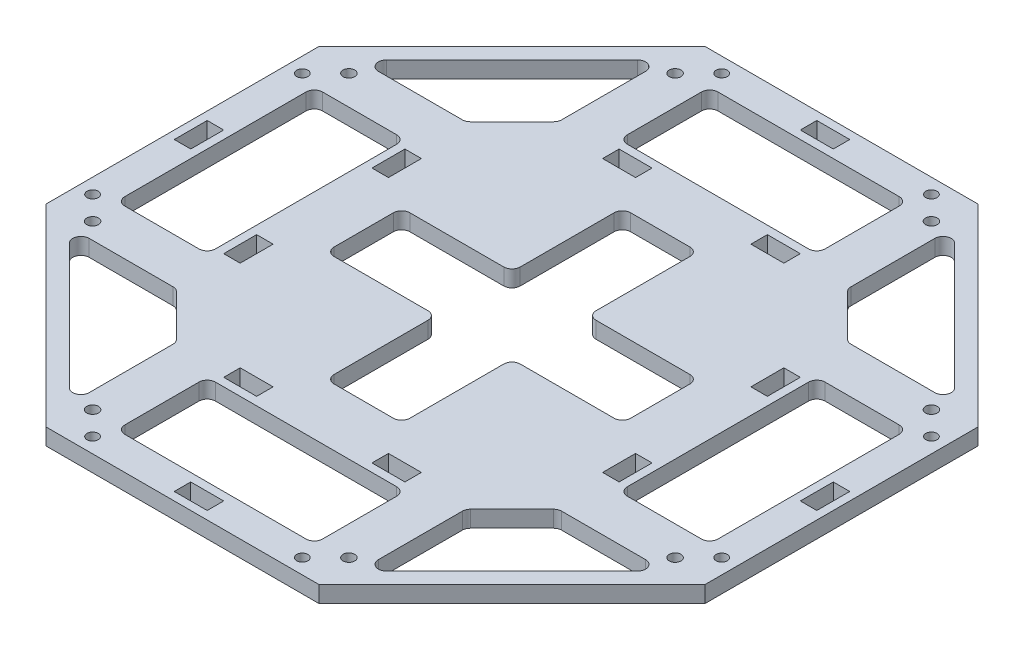
SolidWorks part; units mm, degrees
material "Custom Plastic"
ref_plane "Front Plane" through (0, 0, 0) normal (0, 0, 1) x (1, 0, 0)
ref_plane "Top Plane" through (0, 0, 0) normal (0, 1, 0) x (1, 0, 0)
ref_plane "Right Plane" through (0, 0, 0) normal (1, 0, 0) x (0, 0, -1)
ref_axis "Axis1" through (0, -0.2997, 0) along (0, 1, 0)
sketch "Base sketch" plane through (0, 0, 0) normal (0, 1, 0) x (1, 0, 0)
  line L1 (-127, 52.6051) -> (-127, -52.6051)
  line L2 (-127, -52.6051) -> (-52.6051, -127)
  line L3 (-52.6051, -127) -> (52.6051, -127)
  line L4 (52.6051, -127) -> (127, -52.6051)
  line L5 (127, -52.6051) -> (127, 52.6051)
  line L6 (127, 52.6051) -> (52.6051, 127)
  line L7 (52.6051, 127) -> (-52.6051, 127)
  line L8 (-52.6051, 127) -> (-127, 52.6051)
  circle A0 centre (0, 0) radius 127 construction
  dimension "D1" = 254
extrude "Base" add sketch "Base sketch" along normal blind 6.35
sketch "Sketch3" plane through (0, 6.35, 0) normal (0, 1, 0) x (1, 0, 0)
  line L0 (52.6051, 127) -> (-52.6051, 127) construction
  line L1 (-38.1, 114.3) -> (38.1, 114.3)
  line L2 (-38.1, 114.3) -> (-38.1, 79.375)
  line L4 (-38.1, 79.375) -> (38.1, 79.375)
  line L5 (38.1, 114.3) -> (38.1, 79.375)
  point P6 (0, 79.375)
  dimension "D1" = 76.2
  dimension "D2" = 34.925
  dimension "D3" = 12.7
extrude "Wheel cutout" cut sketch "Sketch3" against normal up to next
fillet "Wheel cutout fillets" radius 3.175 4 edges at (38.1, 3.175, -114.3) (38.1, 3.175, -79.375) (-38.1, 3.175, -79.375) (-38.1, 3.175, -114.3)
pattern_circular "Wheel cutout pattern" count 4 over 360 about axis through (0, -0.2997, 0) along (0, 1, 0) of "Wheel cutout", "Wheel cutout fillets"
sketch "Sketch4" plane through (0, 6.35, 0) normal (0, 1, 0) x (1, 0, 0)
  line L0 (0, 0) -> (0, 127) construction
  line L1 (52.6051, 127) -> (-52.6051, 127) construction
  line L2 (34.925, 120.65) -> (-34.925, 120.65) construction
  line L3 (-34.925, 123.825) -> (-22.225, 123.825) construction
  line L4 (-34.925, 123.825) -> (-34.925, 117.475) construction
  line L5 (-34.925, 117.475) -> (-22.225, 117.475) construction
  line L6 (-22.225, 123.825) -> (-22.225, 117.475) construction
  line L7 (-34.925, 123.825) -> (-22.225, 117.475) construction
  line L8 (-34.925, 117.475) -> (-22.225, 123.825) construction
  line L9 (34.925, 114.3) -> (-34.925, 114.3) construction
  line L10 (34.925, 117.475) -> (22.225, 123.825) construction
  line L11 (34.925, 123.825) -> (22.225, 117.475) construction
  line L12 (22.225, 123.825) -> (22.225, 117.475) construction
  line L13 (34.925, 117.475) -> (22.225, 117.475) construction
  line L14 (34.925, 123.825) -> (34.925, 117.475) construction
  line L15 (34.925, 123.825) -> (22.225, 123.825) construction
  line L16 (-38.1, 96.8375) -> (38.1, 96.8375) construction
  line L17 (-38.1, 111.125) -> (-38.1, 82.55) construction
  line L18 (38.1, 82.55) -> (38.1, 111.125) construction
  line L19 (34.925, 69.85) -> (22.225, 76.2) construction
  line L20 (34.925, 76.2) -> (22.225, 69.85) construction
  line L21 (-34.925, 76.2) -> (-22.225, 69.85) construction
  line L22 (-34.925, 69.85) -> (-22.225, 76.2) construction
  line L23 (34.925, 73.025) -> (-34.925, 73.025) construction
  line L24 (34.925, 69.85) -> (22.225, 69.85)
  line L25 (34.925, 69.85) -> (34.925, 76.2)
  line L26 (34.925, 76.2) -> (22.225, 76.2)
  line L27 (22.225, 69.85) -> (22.225, 76.2)
  line L28 (-22.225, 69.85) -> (-22.225, 76.2)
  line L29 (-34.925, 76.2) -> (-22.225, 76.2)
  line L30 (-34.925, 69.85) -> (-34.925, 76.2)
  line L31 (-34.925, 69.85) -> (-22.225, 69.85)
  line L33 (-6.35, 117.475) -> (6.35, 117.475)
  line L34 (-6.35, 117.475) -> (-6.35, 123.825)
  line L35 (-6.35, 123.825) -> (6.35, 123.825)
  line L36 (6.35, 117.475) -> (6.35, 123.825)
  line L37 (-6.35, 117.475) -> (6.35, 123.825) construction
  line L38 (-6.35, 123.825) -> (6.35, 117.475) construction
  point P5 (-28.575, 120.65)
  point P12 (0, 120.65)
  point P17 (28.575, 120.65)
  point P34 (28.575, 73.025)
  point P35 (-28.575, 73.025)
  point P38 (0, 120.65)
  dimension "D1" = 6.35
  dimension "D2" = 12.7
  dimension "D3" = 69.85
  dimension "D4" = 6.35
  dimension "D5" = 12.7
  dimension "D6" = 6.35
extrude "Support cutouts" cut sketch "Sketch4" against normal up to next
pattern_circular "Support cutout pattern" count 4 over 360 about axis through (0, -0.2997, 0) along (0, 1, 0) of "Support cutouts"
sketch "Sketch5" plane through (0, 6.35, 0) normal (0, 1, 0) x (1, 0, 0)
  line L0 (14.605, 57.15) -> (-14.605, 57.15)
  line L1 (-14.605, 57.15) -> (-14.605, 14.605)
  line L2 (0, 0) -> (0, 57.15) construction
  line L3 (14.605, 14.605) -> (14.605, 57.15)
  line L4 (0, 0) -> (-89.8026, 89.8026) construction
  line L5 (127, 52.6051) -> (52.6051, 127) construction
  line L6 (89.8026, 89.8026) -> (0, 0) construction
  line L7 (-52.6051, 127) -> (-127, 52.6051) construction
  line L8 (22.225, 69.85) -> (34.925, 69.85) construction
  line L9 (-14.605, 14.605) -> (0, 0)
  line L10 (0, 0) -> (14.605, 14.605)
  dimension "D1" = 12.7
  dimension "D2" = 29.21
extrude "Motor Clearance" cut sketch "Sketch5" against normal through all
pattern_circular "CirPattern1" count 4 every 90 about axis through (0, -0.2997, 0) along (0, 1, 0) of "Motor Clearance"
fillet "Fillet1" radius 3.175 12 edges at (-14.605, 3.175, 57.15) (-57.15, 3.175, 14.605) (14.605, 3.175, 57.15) (-14.605, 3.175, 14.605) (14.605, 3.175, 14.605) (14.605, 3.175, -14.605) (57.15, 3.175, 14.605) (57.15, 3.175, -14.605) (14.605, 3.175, -57.15) (-14.605, 3.175, -14.605) (-14.605, 3.175, -57.15) (-57.15, 3.175, -14.605)
sketch "Aligner" [suppressed] plane through (0, 6.35, 0) normal (0, 1, 0) x (1, 0, 0)
  line L0 (74.1687, 87.0459) -> (70.2318, 109.3733)
  line L1 (127, 52.6051) -> (52.6051, 127) construction
  line L2 (70.2318, 109.3733) -> (109.3733, 70.2318)
  line L3 (127, 44.45) -> (109.3733, 70.2318)
  line L4 (89.8026, 89.8026) -> (0, 0) construction
  line L5 (87.0459, 74.1687) -> (109.3733, 70.2318)
  line L6 (70.2318, 109.3733) -> (67.4939, 124.9011)
  line L7 (64.9924, 127) -> (44.45, 127)
  line L9 (109.3733, 70.2318) -> (124.9011, 67.4939)
  line L10 (127, 64.9924) -> (127, 44.45)
  line L11 (52.6051, 127) -> (-52.6051, 127) construction
  line L12 (44.45, 127) -> (70.2318, 109.3733)
  line L13 (38.1, 82.55) -> (38.1, 111.125) construction
  arc A0 (74.1687, 87.0459) -> (87.0459, 74.1687) centre (89.8026, 89.8026) ccw
  arc A1 (124.9011, 67.4939) -> (127, 64.9924) centre (124.46, 64.9924) cw
  arc A2 (67.4939, 124.9011) -> (64.9924, 127) centre (64.9924, 124.46) ccw
  dimension "D1" = 15.875
  dimension "D2" = 2.54
  dimension "D3" = 55
  dimension "D5" = 6.35
sketch "Aligner hole sketch" plane through (0, 6.35, 0) normal (0, 1, 0) x (1, 0, 0)
  line L0 (-89.8026, 89.8026) -> (0, 0) construction
  line L1 (-52.6051, 127) -> (-127, 52.6051) construction
  line L2 (-112.2532, 49.3914) -> (-80.8223, 80.8223) construction
  line L3 (-80.8223, 80.8223) -> (-49.3914, 112.2532) construction
  circle A2 centre (-49.3914, 112.2532) radius 2.2479
  circle A3 centre (-112.2532, 49.3914) radius 2.2479
  dimension "D3" = 4.4958
  dimension "D1" = 12.7
  dimension "D2" = 88.9
extrude "Aligner holes" cut sketch "Aligner hole sketch" against normal through all
pattern_circular "Aligner hole pattern" count 4 over 360 about axis through (0, -0.2997, 0) along (0, 1, 0) of "Aligner holes"
sketch "Sketch7" plane through (0, 6.35, 0) normal (0, 1, 0) x (1, 0, 0)
  circle A0 centre (121.2335, 40.4112) radius 2.1526 construction
  circle A1 centre (121.2335, -40.4112) radius 2.1526 construction
  circle A2 centre (40.4112, -121.2335) radius 2.1526 construction
  circle A3 centre (-40.4112, -121.2335) radius 2.1526 construction
  circle A4 centre (-121.2335, -40.4112) radius 2.1526 construction
  circle A5 centre (-121.2335, 40.4112) radius 2.1526 construction
  circle A6 centre (-40.4112, 121.2335) radius 2.1526 construction
  circle A7 centre (40.4112, 121.2335) radius 2.1527 construction
  circle A8 centre (121.2335, 40.4112) radius 2.1526
  circle A9 centre (121.2335, -40.4112) radius 2.1526
  circle A10 centre (40.4112, -121.2335) radius 2.1526
  circle A11 centre (-40.4112, -121.2335) radius 2.1526
  circle A12 centre (-121.2335, -40.4112) radius 2.1526
  circle A13 centre (-121.2335, 40.4112) radius 2.1526
  circle A14 centre (-40.4112, 121.2335) radius 2.1526
  circle A15 centre (40.4112, 121.2335) radius 2.1527
extrude "Cut-Extrude2" cut sketch "Sketch7" against normal through all
sketch "Sketch8" plane through (0, 6.35, 0) normal (0, 1, 0) x (1, 0, 0)
  line L0 (-109.4634, 61.1615) -> (-61.1615, 109.4634)
  line L1 (-55.7414, 107.2183) -> (-55.7414, 74.8894)
  line L2 (-56.6713, 72.6443) -> (-72.6443, 56.6713)
  line L3 (-74.8894, 55.7414) -> (-107.2183, 55.7414)
  line L4 (-52.6051, 127) -> (-127, 52.6051) construction
  line L5 (0, 0) -> (-64.6578, 64.6578) construction
  line L6 (-64.6578, 64.6578) -> (-85.3124, 85.3124) construction
  line L7 (-85.3124, 85.3124) -> (-89.8026, 89.8026) construction
  circle A0 centre (-112.2532, 49.3914) radius 2.2479 construction
  arc A1 (-109.4634, 61.1615) -> (-107.2183, 55.7414) centre (-107.2183, 58.9164) ccw
  arc A2 (-72.6443, 56.6713) -> (-74.8894, 55.7414) centre (-74.8894, 58.9164) cw
  arc A3 (-55.7414, 74.8894) -> (-56.6713, 72.6443) centre (-58.9164, 74.8894) cw
  arc A4 (-61.1615, 109.4634) -> (-55.7414, 107.2183) centre (-58.9164, 107.2183) cw
  dimension "D4" = 3.175
  dimension "D1" = 6.35
  dimension "D2" = 6.35
  dimension "D3" = 29.21
extrude "Aligher Lightenning holes" cut sketch "Sketch8" against normal through all
pattern_circular "CirPattern3" count 4 every 90 about axis through (0, -0.2997, 0) along (0, 1, 0) of "Aligher Lightenning holes"
equation "\"MAT_THICKNESS\"=0.25"
equation "\"D1@Sketch4\"=\"MAT_THICKNESS\""
equation "\"D1@Base\"=\"MAT_THICKNESS\""
equation "\"D6@Sketch4\"=\"MAT_THICKNESS\""
